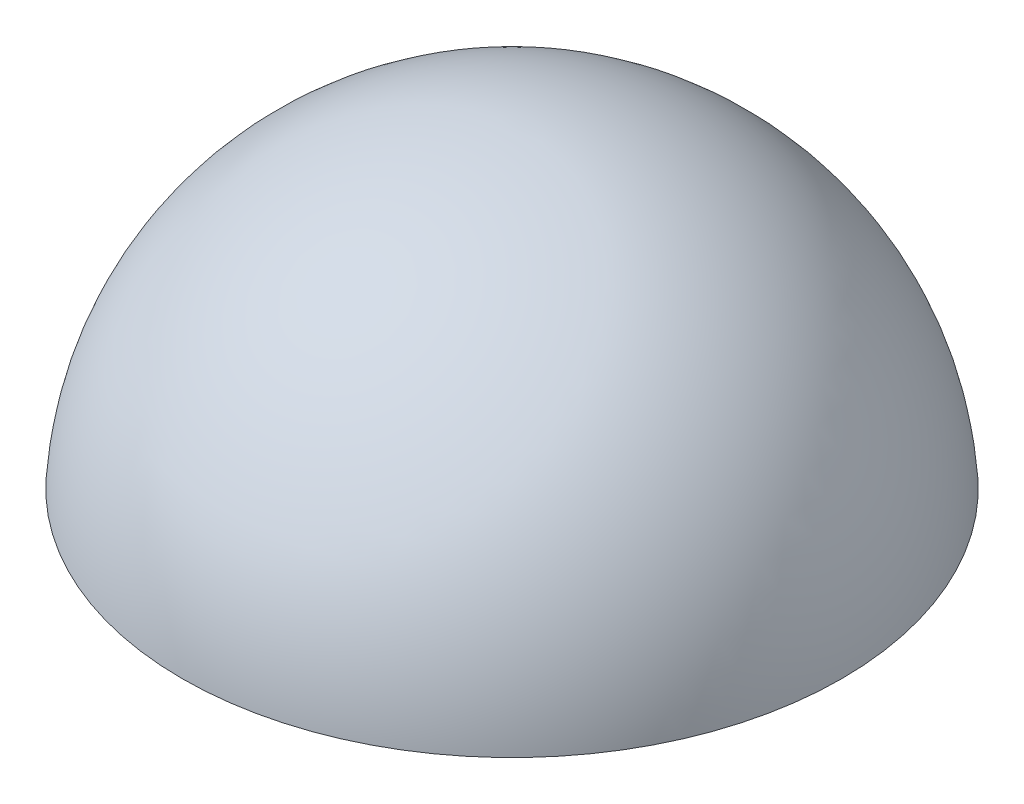
SolidWorks part; units mm, degrees
ref_plane "Front Plane" through (0, 0, 0) normal (0, 0, 1) x (1, 0, 0)
ref_plane "Top Plane" through (0, 0, 0) normal (0, 1, 0) x (1, 0, 0)
ref_plane "Right Plane" through (0, 0, 0) normal (1, 0, 0) x (0, 0, -1)
sketch "Sketch1" plane through (0, 0, 0) normal (0, 0, 1) x (1, 0, 0)
  line L0 (0, 44.2393) -> (0, -6.893) construction
  line L1 (-50.3099, 0) -> (11.9747, 0) construction
  line L2 (-29.9333, 2) -> (0, 2)
  line L3 (0, 2) -> (0, 30)
  arc A0 (-29.9333, 2) -> (0, 30) centre (0, 0) cw
  dimension "D1" = 30
  dimension "D2" = 28
  dimension "D3" = 29.9333
revolve "Revolve7" add sketch "Sketch1" angle 360 about L0
sketch "Sketch2" plane through (0, 2, 0) normal (0, -1, 0) x (1, 0, 0)
  circle A0 centre (0, 0) radius 7.5
  dimension "D1" = 15
extrude "Cut-Extrude1" cut sketch "Sketch2" against normal blind 18 contours A0
thread "Thread1" pitch 2 method extrude trim with start face yes trim with end face yes profile "Thread Profile1" start angle 3, offset 2, length 0, pitch 2, diameter 15
ref_plane "Plane1" through (7.4897, 0, -0.3925) normal (-0.0523, 0, -0.9986) x (-0.9986, 0, 0.0523)
sketch "Thread Profile1" plane through (7.4897, 0, -0.3925) normal (-0.0523, 0, -0.9986) x (-0.9986, 0, 0.0523)
  line L0 (0, 0) -> (0, 2) construction
  line L1 (0, 0) -> (1.0825, 0.625)
  line L2 (1.0825, 0.625) -> (1.0825, 0.875)
  line L3 (1.0825, 0.875) -> (0, 1.5)
  line L4 (1.0825, 0.75) -> (0, 0.75) construction
  line L11 (0, 0) -> (0, 1.5)
  point P2 (0, 0)
  dimension "Pitch" = 2
  dimension "Profile_Angle" = 60
  dimension "Profile_Land" = 0.25
  dimension "Profile_Height" = 1.0825
ref_plane "Plane2" through (0, 30, 0) normal (0, 1, 0) x (1, 0, 0)
sketch "Sketch3" plane through (0, 30, 0) normal (0, 1, 0) x (1, 0, 0)
  line L0 (-29.7825, -3) -> (27.2399, -3) construction
  circle A0 centre (0, 0) radius 29.9333 construction
  text T0 "KABOOM" font "Century Gothic" height in points 22
  dimension "D1" = 3
